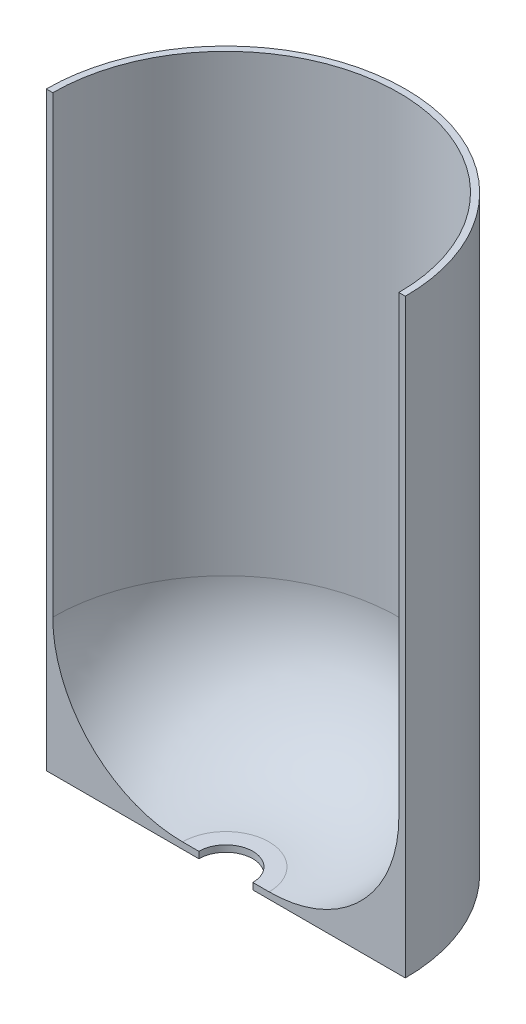
SolidWorks part; units mm, degrees
ref_plane "Front Plane" through (0, 0, 0) normal (0, 0, 1) x (1, 0, 0)
ref_plane "Top Plane" through (0, 0, 0) normal (0, 1, 0) x (1, 0, 0)
ref_plane "Right Plane" through (0, 0, 0) normal (1, 0, 0) x (0, 0, -1)
sketch "Sketch1" plane through (0, 0, 0) normal (0, 1, 0) x (1, 0, 0)
  circle A0 centre (0, 0) radius 26.67
  dimension "D1" = 53.34
extrude "Boss-Extrude1" add sketch "Sketch1" along normal blind 90 contours A0
shell "Shell2" thickness 1
split "Split1" trim tools "Front Plane" bodies to split 101 resulting bodies 107
fillet "Fillet1" radius 20 1 edges at (0, 0, -26.67)
sketch "Sketch2" plane through (0, 0, 0) normal (0, 1, 0) x (1, 0, 0)
  circle A0 centre (0, 0) radius 4.1602
extrude "Cut-Extrude1" cut sketch "Sketch2" against normal blind 10
